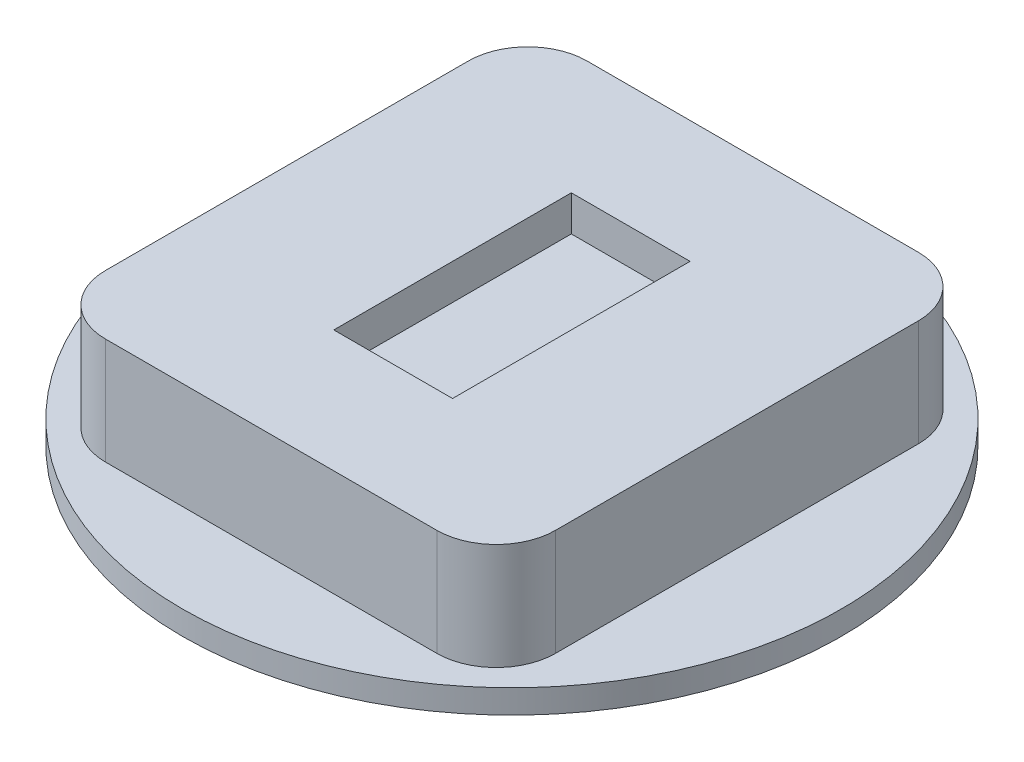
SolidWorks part; units mm, degrees
ref_plane "Front Plane" through (0, 0, 0) normal (0, 0, 1) x (1, 0, 0)
ref_plane "Top Plane" through (0, 0, 0) normal (0, 1, 0) x (1, 0, 0)
ref_plane "Right Plane" through (0, 0, 0) normal (1, 0, 0) x (0, 0, -1)
sketch "Sketch1" plane through (0, 0, 0) normal (0, 1, 0) x (1, 0, 0)
  circle A0 centre (0, 0) radius 277.5
  dimension "D1" = 555
extrude "Boss-Extrude1" add sketch "Sketch1" along normal blind 10 and the other way blind 10
sketch "Sketch2" plane through (0, 10, 0) normal (0, 1, 0) x (1, 0, 0)
  line L1 (189.4746, -202.7452) -> (-189.4746, -202.7452)
  line L2 (189.4746, -202.7452) -> (189.4746, 202.7452)
  line L3 (189.4746, 202.7452) -> (-189.4746, 202.7452)
  line L4 (-189.4746, -202.7452) -> (-189.4746, 202.7452)
  line L5 (189.4746, -202.7452) -> (-189.4746, 202.7452) construction
  line L6 (189.4746, 202.7452) -> (-189.4746, -202.7452) construction
  circle A0 centre (0, 0) radius 277.5 construction
  point P0 (0, 0)
extrude "Boss-Extrude2" add sketch "Sketch2" along normal blind 89.7205 contours L2 L1 L4 L3
sketch "Sketch6" plane through (0, 99.7205, 0) normal (0, 1, 0) x (1, 0, 0)
  line L1 (50, -100) -> (-50, -100)
  line L2 (50, -100) -> (50, 100)
  line L3 (50, 100) -> (-50, 100)
  line L4 (-50, -100) -> (-50, 100)
  line L5 (50, -100) -> (-50, 100) construction
  line L6 (50, 100) -> (-50, -100) construction
  point P0 (0, 0)
extrude "Cut-Extrude4" cut sketch "Sketch6" against normal blind 30
fillet "Fillet2" radius 50 4 edges at (-189.4746, 54.8602, -202.7452) (-189.4746, 54.8602, 202.7452) (189.4746, 54.8602, -202.7452) (189.4746, 54.8602, 202.7452)
